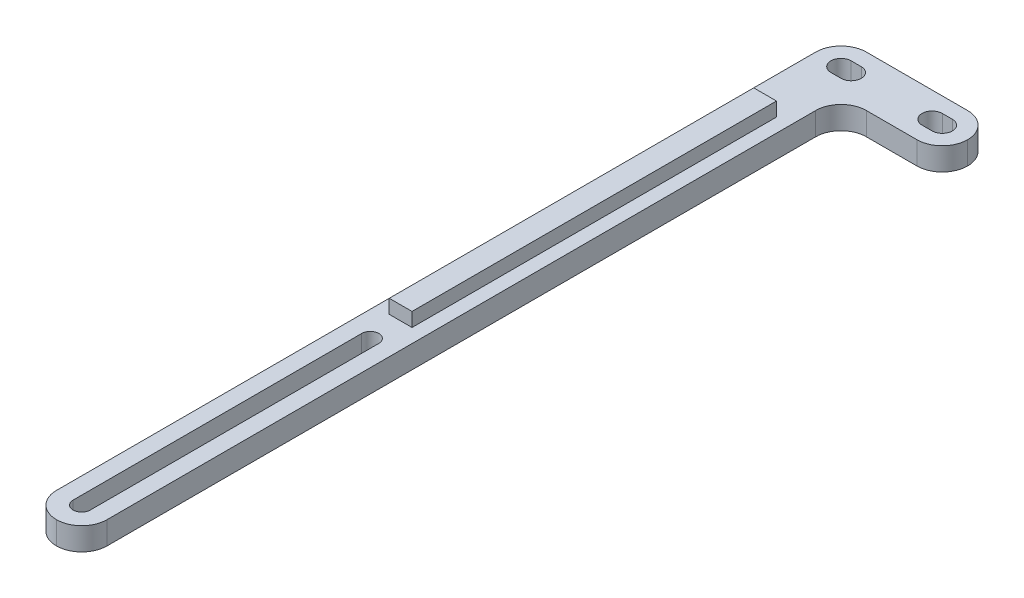
SolidWorks part; units mm, degrees
ref_plane "Front Plane" through (0, 0, 0) normal (0, 0, 1) x (1, 0, 0)
ref_plane "Top Plane" through (0, 0, 0) normal (0, 1, 0) x (1, 0, 0)
ref_plane "Right Plane" through (0, 0, 0) normal (1, 0, 0) x (0, 0, -1)
sketch "Sketch2" plane through (0, 0, 0) normal (0, 1, 0) x (1, 0, 0)
  line L1 (-5, 13.515) -> (5, 13.515)
  line L2 (-5, 13.515) -> (-5, 173.515)
  line L3 (-5, 173.515) -> (5, 173.515)
  line L4 (5, 13.515) -> (5, 173.515)
  line L5 (-5, 13.515) -> (5, 173.515) construction
  line L6 (-5, 173.515) -> (5, 13.515) construction
  point P0 (0, 93.515)
  dimension "D1" = 10
  dimension "D2" = 160
extrude "Boss-Extrude1" add sketch "Sketch2" along normal blind 4.5
sketch "Sketch3" plane through (5, 0, 0) normal (1, 0, 0) x (0, 0, -1)
  line L0 (13.515, 0) -> (173.515, 0) construction
  line L1 (173.515, 4.5) -> (163.515, 4.5)
  line L2 (173.515, 4.5) -> (173.515, 0)
  line L3 (173.515, 0) -> (163.515, 0)
  line L4 (163.515, 4.5) -> (163.515, 0)
  dimension "D1" = 10
extrude "Boss-Extrude2" add sketch "Sketch3" along normal blind 20
fillet "Fillet1" radius 5 2 edges at (5, 2.25, -163.515) (-5, 2.25, -173.515)
fillet "Fillet2" radius 5 2 edges at (-5, 2.25, -13.515) (5, 2.25, -13.515)
fillet "Fillet3" radius 5 2 edges at (25, 2.25, -173.515) (25, 2.25, -163.515)
sketch "Sketch4" plane through (0, 4.5, 0) normal (0, 1, 0) x (1, 0, 0)
  line L0 (0, 18.515) -> (0, 75.515) construction
  line L1 (-1.7, 18.515) -> (-1.7, 75.515)
  line L2 (1.7, 18.515) -> (1.7, 75.515)
  line L3 (-5, 168.515) -> (-5, 18.515) construction
  line L6 (2, 168.515) -> (0, 168.515) construction
  line L7 (2, 166.515) -> (0, 166.515)
  line L8 (2, 170.515) -> (0, 170.515)
  line L9 (18, 168.515) -> (20, 168.515) construction
  line L10 (18, 170.515) -> (20, 170.515)
  line L11 (18, 166.515) -> (20, 166.515)
  arc A0 (-1.7, 18.515) -> (1.7, 18.515) centre (0, 18.515) ccw
  arc A1 (1.7, 75.515) -> (-1.7, 75.515) centre (0, 75.515) ccw
  arc A4 (2, 166.515) -> (2, 170.515) centre (2, 168.515) ccw
  arc A5 (0, 170.515) -> (0, 166.515) centre (0, 168.515) ccw
  arc A6 (18, 170.515) -> (18, 166.515) centre (18, 168.515) ccw
  arc A7 (20, 166.515) -> (20, 170.515) centre (20, 168.515) ccw
  point P4 (0, 47.015)
  point P13 (19, 168.515)
  point P19 (1, 168.515)
  dimension "D1" = 1.7
  dimension "D4" = 2
  dimension "D6" = 2
  dimension "D8" = 18
  dimension "D3" = 5
  dimension "D7" = 2
  dimension "D2" = 57
  dimension "D5" = 2
extrude "Cut-Extrude1" cut sketch "Sketch4" against normal blind 30
sketch "Sketch6" plane through (0, 0, -173.515) normal (0, 0, -1) x (-1, 0, 0)
  line L0 (0, 0) -> (0, 4.5) construction
  line L1 (-2.25, -2.75) -> (2.25, -2.75)
  line L2 (-2.25, -2.75) -> (-2.25, 7.25)
  line L3 (-2.25, 7.25) -> (2.25, 7.25)
  line L4 (2.25, -2.75) -> (2.25, 7.25)
  line L5 (-2.25, -2.75) -> (2.25, 7.25) construction
  line L6 (-2.25, 7.25) -> (2.25, -2.75) construction
  point P0 (0, 2.25)
  dimension "D1" = 10
  dimension "D2" = 4.5
extrude "Boss-Extrude4" add sketch "Sketch6" against normal blind 72 from offset 20 offset against normal yes
